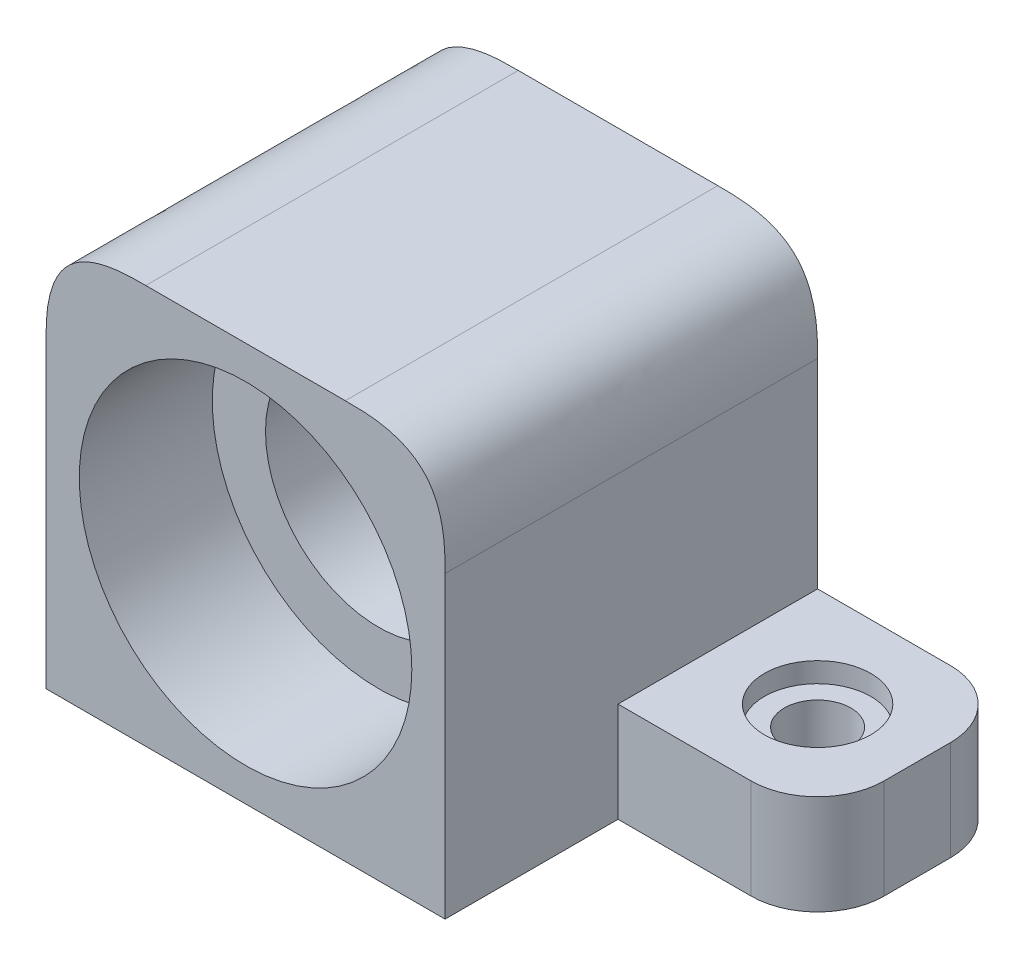
SolidWorks part; units mm, degrees
ref_plane "Front Plane" through (0, 0, 0) normal (0, 0, 1) x (1, 0, 0)
ref_plane "Top Plane" through (0, 0, 0) normal (0, 1, 0) x (1, 0, 0)
ref_plane "Right Plane" through (0, 0, 0) normal (1, 0, 0) x (0, 0, -1)
sketch "Sketch1" plane through (0, 0, 0) normal (0, 0, 1) x (1, 0, 0)
  line L1 (15, -15) -> (-15, -15)
  line L2 (15, -15) -> (15, 15)
  line L3 (15, 15) -> (-15, 15)
  line L4 (-15, -15) -> (-15, 15)
  line L5 (15, -15) -> (-15, 15) construction
  line L6 (15, 15) -> (-15, -15) construction
  point P0 (0, 0)
  dimension "D1" = 30
  dimension "D2" = 30
extrude "Boss-Extrude1" add sketch "Sketch1" along normal blind 20 and the other way blind 8
fillet "Fillet1" radius 7.5 2 edges at (-15, 15, 6) (15, 15, 6) curvature continuous yes
sketch "Sketch2" plane through (0, 0, 0) normal (0, 0, 1) x (1, 0, 0)
  circle A0 centre (0, 0) radius 8.5
  dimension "D1" = 17
extrude "Cut-Extrude1" cut sketch "Sketch2" along normal blind 60
sketch "Sketch3" plane through (15, 0, 0) normal (1, 0, 0) x (0, 0, -1)
  line L1 (8, -15) -> (-7, -15)
  line L2 (8, -15) -> (8, -7.5)
  line L3 (8, -7.5) -> (-7, -7.5)
  line L4 (-7, -15) -> (-7, -7.5)
  dimension "D1" = 7.5
  dimension "D2" = 15
extrude "Boss-Extrude2" add sketch "Sketch3" along normal blind 15
sketch "Sketch5" plane through (-15, 0, 0) normal (-1, 0, 0) x (0, 0, 1)
  line L1 (-8, -15) -> (7, -15)
  line L2 (-8, -15) -> (-8, -7.5)
  line L3 (-8, -7.5) -> (7, -7.5)
  line L4 (7, -15) -> (7, -7.5)
  dimension "D1" = 15
  dimension "D2" = 7.5
extrude "Boss-Extrude4" add sketch "Sketch5" along normal blind 15
sketch "Sketch11" plane through (0, 0, 20) normal (0, 0, 1) x (1, 0, 0)
  circle A0 centre (0, 0) radius 12.5
  dimension "D1" = 25
extrude "Cut-Extrude3" cut sketch "Sketch11" against normal blind 10
sketch "Sketch12" plane through (0, 0, 0) normal (0, 0, 1) x (1, 0, 0)
  circle A0 centre (0, -3.5) radius 3.5
  dimension "D1" = 7
  dimension "D2" = 3.5
extrude "Cut-Extrude4" cut sketch "Sketch12" against normal blind 10 contours A0
fillet "Fillet8" radius 5 4 edges at (30, -11.25, 7) (30, -11.25, -8) (-30, -11.25, 7) (-30, -11.25, -8)
sketch "Sketch15" plane through (0, -7.5, 0) normal (0, 1, 0) x (1, 0, 0)
  line L0 (30, 3) -> (30, -2) construction
  line L1 (-30, -2) -> (-30, 3) construction
  line L2 (25, -7) -> (15, -7) construction
  line L3 (-25, 8) -> (-15, 8) construction
  circle A0 centre (22.5, 0.5) radius 4
  circle A1 centre (-22.5, 0.5) radius 4
  dimension "D2" = 8
  dimension "D3" = 8
  dimension "D1" = 7.5
  dimension "D4" = 7.5
  dimension "D5" = 7.5
  dimension "D6" = 7.5
extrude "Cut-Extrude5" cut sketch "Sketch15" against normal blind 1.5
sketch "Sketch16" plane through (0, -9, 0) normal (0, 1, 0) x (1, 0, 0)
  circle A0 centre (-22.5, 0.5) radius 2.5
  circle A1 centre (22.5, 0.5) radius 2.5
  dimension "D1" = 5
  dimension "D2" = 5
extrude "Cut-Extrude6" cut sketch "Sketch16" against normal blind 12
sketch "Sketch17" plane through (0, 15, 0) normal (0, 1, 0) x (1, 0, 0)
sketch "Sketch18" plane through (0, 0, 0) normal (0, 0, 1) x (1, 0, 0)
  circle A0 centre (0, -3.5) radius 4.25
  dimension "D1" = 8.5
extrude "Cut-Extrude8" cut sketch "Sketch18" against normal blind 1.75 from offset 1.5 offset against normal yes
extrude "Cut-Extrude9" cut sketch "Sketch18<2>" against normal blind 1.5 from offset 5 offset against normal yes
sketch "Sketch18<2>" plane through (0, 0, 0) normal (0, 0, 1) x (1, 0, 0) same geometry as "Sketch18"
equation "\"7.5.000000mm\"=5"
